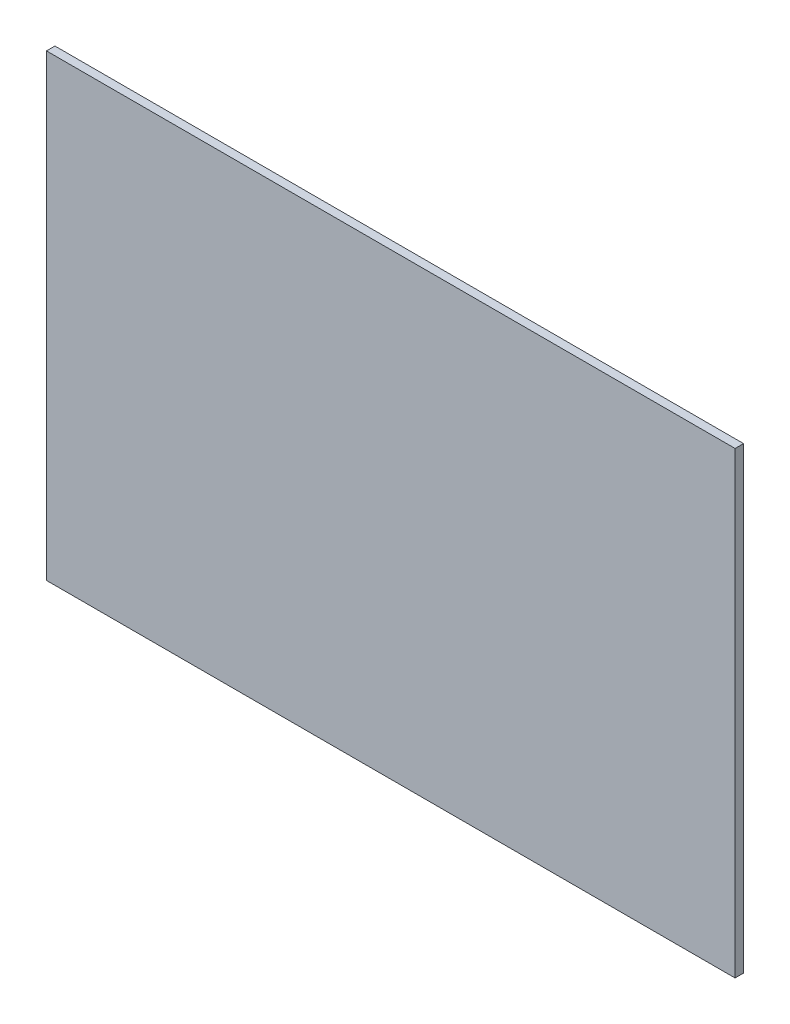
SolidWorks part; units mm, degrees
ref_plane "Front Plane" through (0, 0, 0) normal (0, 0, 1) x (1, 0, 0)
ref_plane "Top Plane" through (0, 0, 0) normal (0, 1, 0) x (1, 0, 0)
ref_plane "Right Plane" through (0, 0, 0) normal (1, 0, 0) x (0, 0, -1)
sketch "Sketch1" plane through (0, 0, 0) normal (0, 0, 1) x (1, 0, 0)
  line L1 (0, 0) -> (2440, 0)
  line L2 (0, 0) -> (0, 1625)
  line L3 (0, 1625) -> (2440, 1625)
  line L4 (2440, 0) -> (2440, 1625)
  dimension "D1" = 2440
  dimension "D2" = 1625
extrude "Boss-Extrude1" add sketch "Sketch1" along normal blind 30
